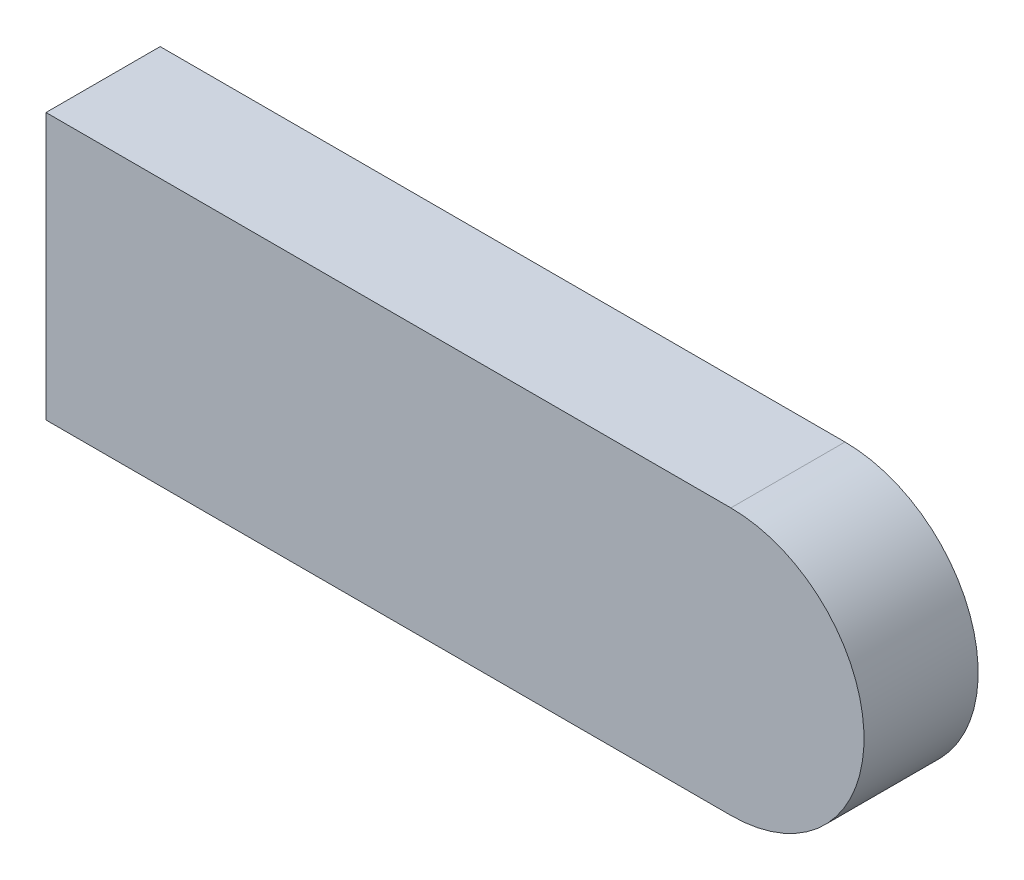
SolidWorks part; units mm, degrees
ref_plane "Front Plane" through (0, 0, 0) normal (0, 0, 1) x (1, 0, 0)
ref_plane "Top Plane" through (0, 0, 0) normal (0, 1, 0) x (1, 0, 0)
ref_plane "Right Plane" through (0, 0, 0) normal (1, 0, 0) x (0, 0, -1)
sketch "Sketch1" plane through (0, 0, 0) normal (0, 0, 1) x (1, 0, 0)
  line L0 (-1166.4945, -285.3198) -> (-1666.5297, 696.0545) construction
  line L1 (1267.3965, 2049.1703) -> (1267.3965, 1979.1703)
  line L2 (1267.3965, 1979.1703) -> (1447.3965, 1979.1703)
  line L4 (1447.3965, 2049.1703) -> (1267.3965, 2049.1703)
  arc A0 (1447.3965, 1979.1703) -> (1447.3965, 2049.1703) centre (1447.3965, 2014.1703) ccw
  dimension "D4" = 35
  dimension "D1" = 70
  dimension "D2" = 180
  dimension "D3" = 180
extrude "Boss-Extrude2" add sketch "Sketch1" along normal blind 30 contours L0 L1 L2 A0 region at (1371.288, 2014.1703, 0)
